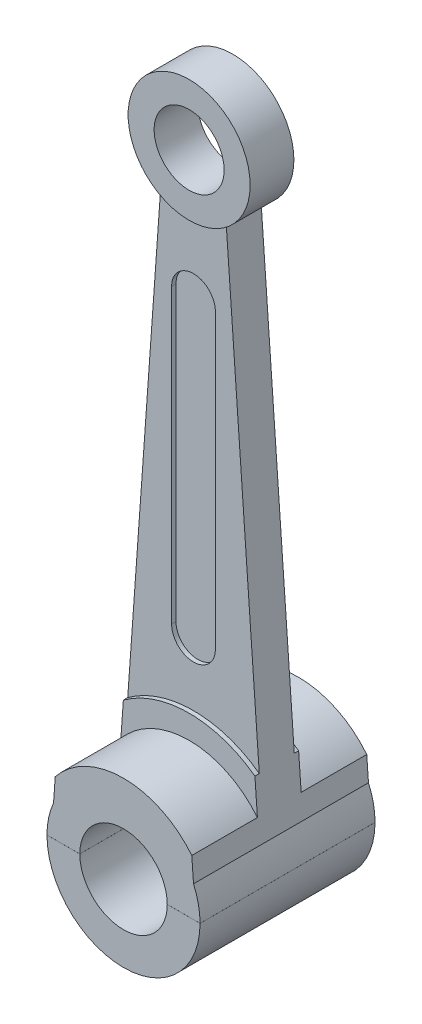
SolidWorks part; units mm, degrees
ref_plane "Front Plane" through (0, 0, 0) normal (0, 0, 1) x (1, 0, 0)
ref_plane "Top Plane" through (0, 0, 0) normal (0, 1, 0) x (1, 0, 0)
ref_plane "Right Plane" through (0, 0, 0) normal (1, 0, 0) x (0, 0, -1)
sketch "Sketch1" plane through (0, 0, 0) normal (0, 0, 1) x (1, 0, 0)
  line L0 (0, 13.69) -> (0, 0) construction
  line L1 (-0.75, 12.5138) -> (-1.65, 1.9285)
  line L2 (0.75, 12.5138) -> (1.65, 1.9285)
  line L3 (0, 10.69) -> (0, 4) construction
  line L4 (0.5, 10.69) -> (0.5, 4)
  line L5 (-0.5, 10.69) -> (-0.5, 4)
  circle A0 centre (0, 0) radius 1
  circle A1 centre (0, 0) radius 2.538
  circle A2 centre (0, 13.69) radius 0.8
  circle A3 centre (0, 13.69) radius 1.395
  arc A4 (0.5, 10.69) -> (-0.5, 10.69) centre (0, 10.69) ccw
  arc A5 (-0.5, 4) -> (0.5, 4) centre (0, 4) ccw
  point P13 (0, 7.345)
  dimension "D1" = 5.076
  dimension "D2" = 2
  dimension "D3" = 1.6
  dimension "D4" = 2.79
  dimension "D7" = 0.5
  dimension "D5" = 13.69
  dimension "D6" = 1.5
  dimension "D8" = 3
  dimension "D9" = 4
  dimension "D10" = 3.3
extrude "Boss-Extrude1" add sketch "Sketch1" along normal mid plane 1 contours A3 A2 | A1 A0 region at (-0.6518, 14.8786, 0) region at (0, 2.4662, 0)
extrude "Boss-Extrude2" add sketch "Sketch1<3>" along normal mid plane 0.8 contours A3 L1 A1 L2 A5 L5 A4 L4 region at (0, 12.1841, 0)
sketch "Sketch1<3>" plane through (0, 0, 0) normal (0, 0, 1) x (1, 0, 0) same geometry as "Sketch1"
extrude "Boss-Extrude3" add sketch "Sketch1<4>" along normal mid plane 0.6 contours L5 A5 L4 A4 region at (0, 7.345, 0)
sketch "Sketch1<4>" plane through (0, 0, 0) normal (0, 0, 1) x (1, 0, 0) same geometry as "Sketch1"
sketch "Sketch2" plane through (0, 0, 0.5) normal (0, 0, 1) x (1, 0, 0)
  circle A0 centre (0, 0) radius 1
  circle A1 centre (0, 0) radius 2
  dimension "D1" = 2
  dimension "D2" = 4
extrude "Boss-Extrude4" add sketch "Sketch2" along normal blind 1.5 and the other way blind 2.5
sketch "Sketch3" plane through (0, 0, 0) normal (0, 0, 1) x (1, 0, 0)
  line L0 (-0.75, 12.5138) -> (-2.8906, 1.9734)
  line L1 (0.75, 12.5138) -> (2.8906, 1.9734)
  line L2 (-0.75, 12.5138) -> (-1.6, 0.7089)
  line L3 (0.75, 12.5138) -> (1.6, 0.7089)
  arc A0 (-1.6, 0.7089) -> (1.6, 0.7089) centre (0, 0) ccw
  arc A1 (-2.8906, 1.9734) -> (2.8906, 1.9734) centre (0, 0) ccw
  dimension "D2" = 1.75
  dimension "D3" = 3.5
  dimension "D1" = 3.2
extrude "Cut-Extrude1" cut sketch "Sketch3" against normal mid plane 14.2
sketch "Sketch4" plane through (0, 0, 0) normal (0, 0, 1) x (1, 0, 0)
  line L0 (0, 0) -> (5.2174, 0) construction
  line L2 (5.2174, 0) -> (-4.6777, 0)
  line L3 (5.2174, 0) -> (5.2174, 0.001)
  line L4 (5.2174, 0.001) -> (-4.6777, 0.001)
  line L5 (-4.6777, 0) -> (-4.6777, 0.001)
  dimension "D1" = 0.001
extrude "Cut-Extrude4" cut sketch "Sketch4" against normal mid plane 21.82 contours L5 L2 L3 L4 region at (0.2699, 0.0005, 0)
